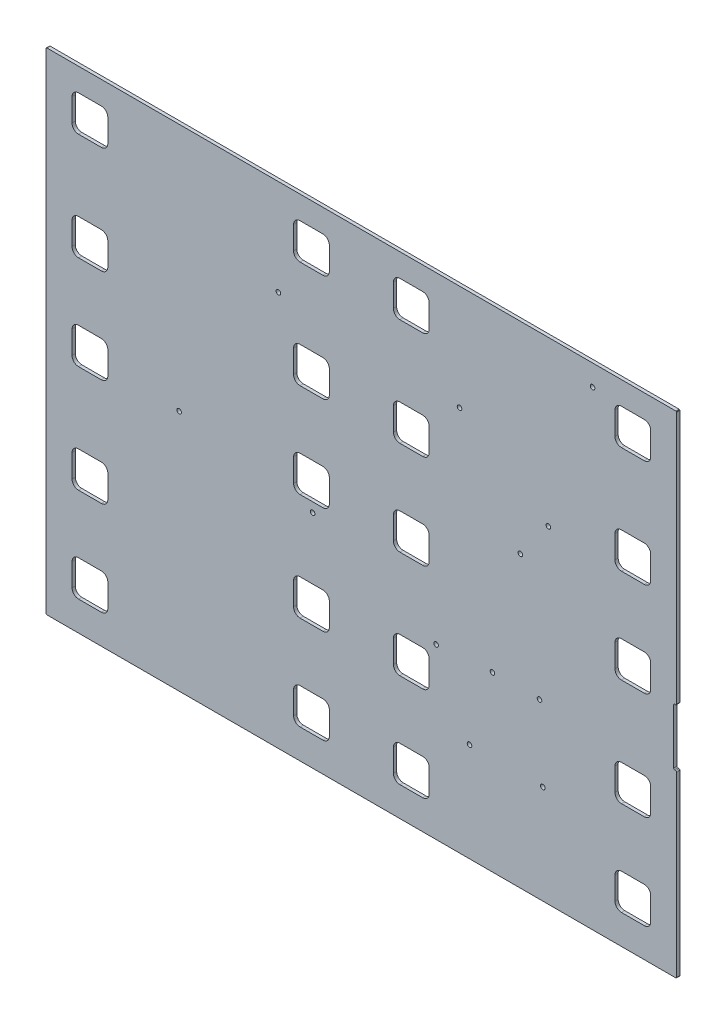
SolidWorks part; units mm, degrees
material "PP Film"
ref_plane "X-Y Datum" through (0, 0, 0) normal (0, 0, 1) x (1, 0, 0)
ref_plane "X-Z Datum" through (0, 0, 0) normal (0, 1, 0) x (1, 0, 0)
ref_plane "Y-Z Datum" through (0, 0, 0) normal (1, 0, 0) x (0, 0, -1)
sketch "Sketch9" plane through (0, 0, 0) normal (0, 0, 1) x (1, 0, 0)
  line L0 (-82.7559, -182.5893) -> (-82.7583, -160.1613) construction
  line L1 (-89.109, -153.8119) -> (-111.537, -153.8143) construction
  line L2 (-117.8863, -160.165) -> (-117.8839, -182.593) construction
  line L3 (-111.5333, -188.9423) -> (-89.1053, -188.9399) construction
  line L4 (475.4266, 171.7866) -> (-142.9187, 171.7216)
  line L12 (-111.5443, -83.8117) -> (-89.1163, -83.8093) construction
  line L13 (-82.767, -77.4587) -> (-82.7693, -55.0307) construction
  line L14 (-89.12, -48.6813) -> (-111.548, -48.6837) construction
  line L15 (-117.8973, -55.0344) -> (-117.895, -77.4624) construction
  line L16 (-82.7877, 120.2549) -> (-82.7901, 142.6829) construction
  line L17 (-89.1408, 149.0323) -> (-111.5688, 149.0299) construction
  line L18 (-117.9181, 142.6792) -> (-117.9157, 120.2512) construction
  line L19 (-111.5651, 113.9019) -> (-89.1371, 113.9043) construction
  line L20 (-111.554, 8.7713) -> (-89.126, 8.7737) construction
  line L21 (-117.9071, 37.5486) -> (-117.9047, 15.1206) construction
  line L22 (-89.1297, 43.9017) -> (-111.5577, 43.8993) construction
  line L23 (-82.7767, 15.1243) -> (-82.7791, 37.5523) construction
  line L24 (-82.7559, -182.5893) -> (-82.7583, -160.1613)
  line L25 (-89.109, -153.8119) -> (-111.537, -153.8143)
  line L26 (-117.8863, -160.165) -> (-117.8839, -182.593)
  line L27 (-111.5333, -188.9423) -> (-89.1053, -188.9399)
  line L28 (-111.5443, -83.8117) -> (-89.1163, -83.8093)
  line L29 (-82.767, -77.4587) -> (-82.7693, -55.0307)
  line L30 (-89.12, -48.6813) -> (-111.548, -48.6837)
  line L31 (-117.8973, -55.0344) -> (-117.895, -77.4624)
  line L32 (-82.7877, 120.2549) -> (-82.7901, 142.6829)
  line L33 (-89.1408, 149.0323) -> (-111.5688, 149.0299)
  line L34 (-117.9181, 142.6792) -> (-117.9157, 120.2512)
  line L35 (-111.5651, 113.9019) -> (-89.1371, 113.9043)
  line L36 (-111.554, 8.7713) -> (-89.126, 8.7737)
  line L37 (-117.9071, 37.5486) -> (-117.9047, 15.1206)
  line L38 (-89.1297, 43.9017) -> (-111.5577, 43.8993)
  line L39 (-82.7767, 15.1243) -> (-82.7791, 37.5523)
  line L40 (-82.7462, -275.1723) -> (-82.7486, -252.7443) construction
  line L41 (-89.0992, -246.3949) -> (-111.5272, -246.3973) construction
  line L42 (-117.8766, -252.748) -> (-117.8742, -275.176) construction
  line L43 (-111.5235, -281.5253) -> (-89.0955, -281.5229) construction
  line L44 (-82.7462, -275.1723) -> (-82.7486, -252.7443)
  line L45 (-89.0992, -246.3949) -> (-111.5272, -246.3973)
  line L46 (-117.8766, -252.748) -> (-117.8742, -275.176)
  line L47 (-111.5235, -281.5253) -> (-89.0955, -281.5229)
  line L174 (475.4266, 171.7866) -> (-142.9187, 171.7216)
  line L243 (-143.3593, 171.281) -> (-143.3088, -310.0568)
  line L244 (-143.3593, 171.281) -> (-143.3088, -310.0568)
  line L245 (-142.8681, -310.4974) -> (475.4773, -310.4324)
  line L246 (-142.8681, -310.4974) -> (475.4773, -310.4324)
  line L247 (475.9178, -309.9918) -> (475.8673, 171.346)
  line L248 (475.9178, -309.9918) -> (475.8673, 171.346)
  arc A0 (-89.1053, -188.9399) -> (-82.7559, -182.5893) centre (-89.1059, -182.5899) ccw construction
  arc A1 (-82.7583, -160.1613) -> (-89.109, -153.8119) centre (-89.1083, -160.1619) ccw construction
  arc A2 (-111.537, -153.8143) -> (-117.8863, -160.165) centre (-111.5363, -160.1643) ccw construction
  arc A3 (-117.8839, -182.593) -> (-111.5333, -188.9423) centre (-111.5339, -182.5923) ccw construction
  arc A4 (-89.1163, -83.8093) -> (-82.767, -77.4587) centre (-89.117, -77.4593) ccw construction
  arc A5 (-82.7693, -55.0307) -> (-89.12, -48.6813) centre (-89.1193, -55.0313) ccw construction
  arc A6 (-111.548, -48.6837) -> (-117.8973, -55.0344) centre (-111.5473, -55.0337) ccw construction
  arc A7 (-117.895, -77.4624) -> (-111.5443, -83.8117) centre (-111.545, -77.4617) ccw construction
  arc A8 (-89.1371, 113.9043) -> (-82.7877, 120.2549) centre (-89.1377, 120.2543) ccw construction
  arc A9 (-82.7901, 142.6829) -> (-89.1408, 149.0323) centre (-89.1401, 142.6823) ccw construction
  arc A10 (-111.5688, 149.0299) -> (-117.9181, 142.6792) centre (-111.5681, 142.6799) ccw construction
  arc A11 (-117.9157, 120.2512) -> (-111.5651, 113.9019) centre (-111.5657, 120.2519) ccw construction
  arc A12 (-82.7791, 37.5523) -> (-89.1297, 43.9017) centre (-89.1291, 37.5517) ccw construction
  arc A13 (-89.126, 8.7737) -> (-82.7767, 15.1243) centre (-89.1267, 15.1237) ccw construction
  arc A14 (-117.9047, 15.1206) -> (-111.554, 8.7713) centre (-111.5547, 15.1213) ccw construction
  arc A15 (-111.5577, 43.8993) -> (-117.9071, 37.5486) centre (-111.5571, 37.5493) ccw construction
  arc A16 (-89.1053, -188.9399) -> (-82.7559, -182.5893) centre (-89.1059, -182.5899) ccw
  arc A17 (-82.7583, -160.1613) -> (-89.109, -153.8119) centre (-89.1083, -160.1619) ccw
  arc A18 (-111.537, -153.8143) -> (-117.8863, -160.165) centre (-111.5363, -160.1643) ccw
  arc A19 (-117.8839, -182.593) -> (-111.5333, -188.9423) centre (-111.5339, -182.5923) ccw
  arc A20 (-89.1163, -83.8093) -> (-82.767, -77.4587) centre (-89.117, -77.4593) ccw
  arc A21 (-82.7693, -55.0307) -> (-89.12, -48.6813) centre (-89.1193, -55.0313) ccw
  arc A22 (-111.548, -48.6837) -> (-117.8973, -55.0344) centre (-111.5473, -55.0337) ccw
  arc A23 (-117.895, -77.4624) -> (-111.5443, -83.8117) centre (-111.545, -77.4617) ccw
  arc A24 (-89.1371, 113.9043) -> (-82.7877, 120.2549) centre (-89.1377, 120.2543) ccw
  arc A25 (-82.7901, 142.6829) -> (-89.1408, 149.0323) centre (-89.1401, 142.6823) ccw
  arc A26 (-111.5688, 149.0299) -> (-117.9181, 142.6792) centre (-111.5681, 142.6799) ccw
  arc A27 (-117.9157, 120.2512) -> (-111.5651, 113.9019) centre (-111.5657, 120.2519) ccw
  arc A28 (-82.7791, 37.5523) -> (-89.1297, 43.9017) centre (-89.1291, 37.5517) ccw
  arc A29 (-89.126, 8.7737) -> (-82.7767, 15.1243) centre (-89.1267, 15.1237) ccw
  arc A30 (-117.9047, 15.1206) -> (-111.554, 8.7713) centre (-111.5547, 15.1213) ccw
  arc A31 (-111.5577, 43.8993) -> (-117.9071, 37.5486) centre (-111.5571, 37.5493) ccw
  arc A32 (-89.0955, -281.5229) -> (-82.7462, -275.1723) centre (-89.0962, -275.1729) ccw construction
  arc A33 (-111.5272, -246.3973) -> (-117.8766, -252.748) centre (-111.5266, -252.7473) ccw construction
  arc A34 (-117.8742, -275.176) -> (-111.5235, -281.5253) centre (-111.5242, -275.1753) ccw construction
  arc A35 (-89.0955, -281.5229) -> (-82.7462, -275.1723) centre (-89.0962, -275.1729) ccw
  arc A36 (-111.5272, -246.3973) -> (-117.8766, -252.748) centre (-111.5266, -252.7473) ccw
  arc A37 (-117.8742, -275.176) -> (-111.5235, -281.5253) centre (-111.5242, -275.1753) ccw
  arc A38 (-82.7486, -252.7443) -> (-89.0992, -246.3949) centre (-89.0986, -252.7449) ccw construction
  arc A39 (-82.7486, -252.7443) -> (-89.0992, -246.3949) centre (-89.0986, -252.7449) ccw
  arc A72 (-142.8681, -310.4974) -> (-143.3088, -310.0568) centre (-144.189, -311.3779) ccw
  arc A108 (-142.8681, -310.4974) -> (-143.3088, -310.0568) centre (-144.189, -311.3779) ccw
  arc A128 (475.9178, -309.9918) -> (475.4773, -310.4324) centre (476.7984, -311.3127) ccw
  arc A132 (475.9178, -309.9918) -> (475.4773, -310.4324) centre (476.7984, -311.3127) ccw
  arc A136 (475.4266, 171.7866) -> (475.8673, 171.346) centre (476.7475, 172.6671) ccw
  arc A140 (475.4266, 171.7866) -> (475.8673, 171.346) centre (476.7475, 172.6671) ccw
  arc A142 (-143.3593, 171.281) -> (-142.9187, 171.7216) centre (-144.2398, 172.6019) ccw
  arc A144 (-143.3593, 171.281) -> (-142.9187, 171.7216) centre (-144.2398, 172.6019) ccw
  dimension "D1" = 0
extrude "Boss-Extrude2" add sketch "Sketch9" along normal blind 3.175 contours L244 L246 L174 A39 L44 A35 L47 A37 L46 A36 L45 A31 L38 A28 L39 A29 L36 A30 L37 A27 L34 A26 L33 A25 L32 A24 L35 A23 L31 A22 L30 A21 L29 A20 L28 A19 L26 A18 L25 A17 L24 A16 L27 | L44 A39 L45 A36 L46 A37 L47 A35 | L26 A19 L27 A16 L24 A17 L25 A18 | L38 A31 L37 A30 L36 A29 L39 A28 | L34 A27 L35 A24 L32 A25 L33 A26 | L31 A23 L28 A20 L29 A21 L30 A22 region at (171.7433, -69.3677, 0) region at (-100.3211, -171.3771, 0) region at (-100.3322, -66.2465, 0) region at (-100.3529, 131.4671, 0) region at (-100.3419, 26.3365, 0) region at (-100.3114, -263.9601, 0)
sketch "Sketch10" plane through (0, 0, 3.175) normal (0, 0, 1) x (1, 0, 0)
  line L9 (476.8831, 172.8027) -> (-144.3755, 172.7375)
  line L10 (-144.3755, 172.7375) -> (-144.3246, -311.5135)
  line L11 (-144.3246, -311.5135) -> (476.934, -311.4483)
  line L12 (-117.8863, -160.165) -> (-117.8839, -182.593)
  line L13 (-111.5333, -188.9423) -> (-89.1053, -188.9399)
  line L14 (-82.7559, -182.5893) -> (-82.7583, -160.1613)
  line L15 (-89.109, -153.8119) -> (-111.537, -153.8143)
  line L16 (-117.8863, -160.165) -> (-117.8839, -182.593)
  line L17 (-111.5333, -188.9423) -> (-89.1053, -188.9399)
  line L18 (-82.7559, -182.5893) -> (-82.7583, -160.1613)
  line L19 (-89.109, -153.8119) -> (-111.537, -153.8143)
  line L20 (-117.8766, -252.748) -> (-117.8742, -275.176)
  line L21 (-89.0992, -246.3949) -> (-111.5272, -246.3973)
  line L22 (-82.7462, -275.1723) -> (-82.7486, -252.7443)
  line L23 (-111.5235, -281.5253) -> (-89.0955, -281.5229)
  line L24 (-117.8766, -252.748) -> (-117.8742, -275.176)
  line L25 (-89.0992, -246.3949) -> (-111.5272, -246.3973)
  line L26 (-82.7462, -275.1723) -> (-82.7486, -252.7443)
  line L27 (-111.5235, -281.5253) -> (-89.0955, -281.5229)
  line L28 (-89.12, -48.6813) -> (-111.548, -48.6837)
  line L29 (-117.8973, -55.0344) -> (-117.895, -77.4624)
  line L30 (-111.5443, -83.8117) -> (-89.1163, -83.8093)
  line L31 (-82.767, -77.4587) -> (-82.7693, -55.0307)
  line L32 (-89.12, -48.6813) -> (-111.548, -48.6837)
  line L33 (-117.8973, -55.0344) -> (-117.895, -77.4624)
  line L34 (-111.5443, -83.8117) -> (-89.1163, -83.8093)
  line L35 (-82.767, -77.4587) -> (-82.7693, -55.0307)
  line L36 (-82.7877, 120.2549) -> (-82.7901, 142.6829)
  line L37 (-111.5651, 113.9019) -> (-89.1371, 113.9043)
  line L38 (-117.9181, 142.6792) -> (-117.9157, 120.2512)
  line L39 (-89.1408, 149.0323) -> (-111.5688, 149.0299)
  line L40 (-82.7877, 120.2549) -> (-82.7901, 142.6829)
  line L41 (-111.5651, 113.9019) -> (-89.1371, 113.9043)
  line L42 (-117.9181, 142.6792) -> (-117.9157, 120.2512)
  line L43 (-89.1408, 149.0323) -> (-111.5688, 149.0299)
  line L44 (-111.554, 8.7713) -> (-89.126, 8.7737)
  line L45 (-82.7767, 15.1243) -> (-82.7791, 37.5523)
  line L46 (-89.1297, 43.9017) -> (-111.5577, 43.8993)
  line L47 (-117.9071, 37.5486) -> (-117.9047, 15.1206)
  line L48 (-111.554, 8.7713) -> (-89.126, 8.7737)
  line L49 (-82.7767, 15.1243) -> (-82.7791, 37.5523)
  line L50 (-89.1297, 43.9017) -> (-111.5577, 43.8993)
  line L51 (-117.9071, 37.5486) -> (-117.9047, 15.1206)
  line L53 (476.934, -311.4483) -> (476.8831, 172.8027)
  arc A4 (-117.8839, -182.593) -> (-111.5333, -188.9423) centre (-111.5339, -182.5923) ccw
  arc A5 (-89.1053, -188.9399) -> (-82.7559, -182.5893) centre (-89.1059, -182.5899) ccw
  arc A6 (-82.7583, -160.1613) -> (-89.109, -153.8119) centre (-89.1083, -160.1619) ccw
  arc A7 (-111.537, -153.8143) -> (-117.8863, -160.165) centre (-111.5363, -160.1643) ccw
  arc A8 (-117.8839, -182.593) -> (-111.5333, -188.9423) centre (-111.5339, -182.5923) ccw
  arc A9 (-89.1053, -188.9399) -> (-82.7559, -182.5893) centre (-89.1059, -182.5899) ccw
  arc A10 (-82.7583, -160.1613) -> (-89.109, -153.8119) centre (-89.1083, -160.1619) ccw
  arc A11 (-111.537, -153.8143) -> (-117.8863, -160.165) centre (-111.5363, -160.1643) ccw
  arc A12 (-111.5272, -246.3973) -> (-117.8766, -252.748) centre (-111.5266, -252.7473) ccw
  arc A13 (-82.7486, -252.7443) -> (-89.0992, -246.3949) centre (-89.0986, -252.7449) ccw
  arc A14 (-89.0955, -281.5229) -> (-82.7462, -275.1723) centre (-89.0962, -275.1729) ccw
  arc A15 (-117.8742, -275.176) -> (-111.5235, -281.5253) centre (-111.5242, -275.1753) ccw
  arc A16 (-111.5272, -246.3973) -> (-117.8766, -252.748) centre (-111.5266, -252.7473) ccw
  arc A17 (-82.7486, -252.7443) -> (-89.0992, -246.3949) centre (-89.0986, -252.7449) ccw
  arc A18 (-89.0955, -281.5229) -> (-82.7462, -275.1723) centre (-89.0962, -275.1729) ccw
  arc A19 (-117.8742, -275.176) -> (-111.5235, -281.5253) centre (-111.5242, -275.1753) ccw
  arc A20 (-111.548, -48.6837) -> (-117.8973, -55.0344) centre (-111.5473, -55.0337) ccw
  arc A21 (-117.895, -77.4624) -> (-111.5443, -83.8117) centre (-111.545, -77.4617) ccw
  arc A22 (-89.1163, -83.8093) -> (-82.767, -77.4587) centre (-89.117, -77.4593) ccw
  arc A23 (-82.7693, -55.0307) -> (-89.12, -48.6813) centre (-89.1193, -55.0313) ccw
  arc A24 (-111.548, -48.6837) -> (-117.8973, -55.0344) centre (-111.5473, -55.0337) ccw
  arc A25 (-117.895, -77.4624) -> (-111.5443, -83.8117) centre (-111.545, -77.4617) ccw
  arc A26 (-89.1163, -83.8093) -> (-82.767, -77.4587) centre (-89.117, -77.4593) ccw
  arc A27 (-82.7693, -55.0307) -> (-89.12, -48.6813) centre (-89.1193, -55.0313) ccw
  arc A28 (-89.1371, 113.9043) -> (-82.7877, 120.2549) centre (-89.1377, 120.2543) ccw
  arc A29 (-117.9157, 120.2512) -> (-111.5651, 113.9019) centre (-111.5657, 120.2519) ccw
  arc A30 (-111.5688, 149.0299) -> (-117.9181, 142.6792) centre (-111.5681, 142.6799) ccw
  arc A31 (-82.7901, 142.6829) -> (-89.1408, 149.0323) centre (-89.1401, 142.6823) ccw
  arc A32 (-89.1371, 113.9043) -> (-82.7877, 120.2549) centre (-89.1377, 120.2543) ccw
  arc A33 (-117.9157, 120.2512) -> (-111.5651, 113.9019) centre (-111.5657, 120.2519) ccw
  arc A34 (-111.5688, 149.0299) -> (-117.9181, 142.6792) centre (-111.5681, 142.6799) ccw
  arc A35 (-82.7901, 142.6829) -> (-89.1408, 149.0323) centre (-89.1401, 142.6823) ccw
  arc A36 (-89.126, 8.7737) -> (-82.7767, 15.1243) centre (-89.1267, 15.1237) ccw
  arc A37 (-82.7791, 37.5523) -> (-89.1297, 43.9017) centre (-89.1291, 37.5517) ccw
  arc A38 (-111.5577, 43.8993) -> (-117.9071, 37.5486) centre (-111.5571, 37.5493) ccw
  arc A39 (-117.9047, 15.1206) -> (-111.554, 8.7713) centre (-111.5547, 15.1213) ccw
  arc A40 (-89.126, 8.7737) -> (-82.7767, 15.1243) centre (-89.1267, 15.1237) ccw
  arc A41 (-82.7791, 37.5523) -> (-89.1297, 43.9017) centre (-89.1291, 37.5517) ccw
  arc A42 (-111.5577, 43.8993) -> (-117.9071, 37.5486) centre (-111.5571, 37.5493) ccw
  arc A43 (-117.9047, 15.1206) -> (-111.554, 8.7713) centre (-111.5547, 15.1213) ccw
  dimension "D2" = 0
  dimension "D3" = 0
  dimension "D4" = 0
  dimension "D5" = 0
  dimension "D6" = 0
extrude "Cut-Extrude6" cut sketch "Sketch10" against normal through all contours L40 A35 L43 A34 L42 A33 L41 A32 | L51 A43 L48 A40 L49 A41 L50 A42 | L35 A27 L32 A24 L33 A25 L34 A26 | L19 A11 L16 A8 L17 A9 L18 A10 | L24 A19 L27 A18 L26 A17 L25 A16 region at (-100.3211, -171.3771, 3.175) region at (-100.3114, -263.9601, 3.175) region at (-100.3322, -66.2465, 3.175) region at (-100.3529, 131.4671, 3.175) region at (-100.3419, 26.3365, 3.175)
pattern_linear "LPattern2" count 2 spacing 217.5764 along (1, 0.0001, 0) of "Cut-Extrude6"
ref_plane "Plane1" through (166.272, 0.0175, 0) normal (-1, -0.0001, 0) x (0, 0, 1)
mirror "Mirror1" about plane through (166.272, 0.0175, 0) normal (-1, -0.0001, 0) of "LPattern2", "Cut-Extrude6"
sketch "Sketch11" plane through (0, 0, 3.175) normal (0, 0, 1) x (1, 0, 0)
  circle A3 centre (295.0226, -140.5889) radius 1.5875
  circle A5 centre (295.0226, -140.5889) radius 1.5875
  circle A7 centre (393.3194, 151.1404) radius 1.5875
  circle A9 centre (393.3194, 151.1404) radius 1.5875
  circle A11 centre (262.6756, 68.3417) radius 1.5875
  circle A13 centre (262.6756, 68.3417) radius 1.5875
  circle A15 centre (84.813, 77.608) radius 1.5875
  circle A17 centre (84.813, 77.608) radius 1.5875
  circle A19 centre (-12.7212, -72.4022) radius 1.5875
  circle A21 centre (-12.7212, -72.4022) radius 1.5875
  circle A23 centre (349.9236, 11.0749) radius 1.5875
  circle A44 centre (349.9236, 11.0749) radius 1.5875
  circle A45 centre (322.4275, -26.052) radius 1.5875
  circle A46 centre (322.4275, -26.052) radius 1.5875
  circle A47 centre (341.2226, -140.584) radius 1.5875
  circle A48 centre (341.2226, -140.584) radius 1.5875
  circle A49 centre (344.4952, -213.3337) radius 1.5875
  circle A50 centre (344.4952, -213.3337) radius 1.5875
  circle A51 centre (118.3901, -93.0713) radius 1.5875
  circle A52 centre (118.3901, -93.0713) radius 1.5875
  circle A53 centre (239.6805, -144.4936) radius 1.5875
  circle A54 centre (239.6805, -144.4936) radius 1.5875
  circle A55 centre (272.4952, -213.3413) radius 1.5875
  circle A56 centre (272.4952, -213.3413) radius 1.5875
  dimension "D1" = 0
  dimension "D2" = 0
  dimension "D3" = 0
  dimension "D4" = 0
  dimension "D5" = 0
  dimension "D6" = 0
  dimension "D7" = 0
  dimension "D8" = 0
  dimension "D9" = 0
  dimension "D10" = 0
  dimension "D11" = 0
  dimension "D12" = 0
sketch "Sketch12" plane through (0, 0, 3.175) normal (0, 0, 1) x (1, 0, 0)
  line L0 (472.9633, -129.0942) -> (472.9585, -83.0942)
  line L1 (472.9632, -127.919) -> (472.9635, -130.2694) construction
  line L2 (472.9584, -81.919) -> (472.9586, -84.2694) construction
  line L3 (475.9178, -309.9918) -> (475.8673, 171.346) construction
  line L4 (472.9609, -78.1542) -> (472.9609, -134.0342)
  line L5 (472.9609, -134.0342) -> (475.8994, -134.0342)
  line L6 (472.9609, -78.1542) -> (475.8935, -78.1542)
  line L9 (475.9178, -309.9918) -> (475.8673, 171.346)
  point P11 (472.9609, -106.0942)
  dimension "D1" = 46
  dimension "D2" = 55.88
extrude "Cut-Extrude8" cut sketch "Sketch12" against normal through all contours L9 region at (474.4287, -106.1035, 3.175)
hole_wizard "M4 Clearance Hole1" positions "Sketch13" profile "Sketch14" hole size "M4" standard "ANSI Metric" end condition through all
sketch "Sketch13" plane through (0, 0, 3.175) normal (0, 0, 1) x (1, 0, 0)
  point P0 (-12.7212, -72.4022)
  point P3 (118.3901, -93.0713)
  point P6 (272.4952, -213.3413)
  point P9 (344.4952, -213.3337)
  point P12 (239.6805, -144.4936)
  point P15 (295.0226, -140.5889)
  point P18 (341.2226, -140.584)
  point P21 (322.4275, -26.052)
  point P24 (349.9236, 11.0749)
  point P27 (262.6756, 68.3417)
  point P30 (393.3194, 151.1404)
  point P33 (84.813, 77.608)
sketch "Sketch14" plane through (-12.7212, -72.4022, 3.175) normal (1, 0, 0) x (0, -1, 0)
  line L0 (0, 0) -> (0, 3.175)
  line L1 (0, 3.175) -> (2.25, 3.175)
  line L2 (2.25, 3.175) -> (2.25, 0)
  line L5 (2.25, 0) -> (0, 0)
  line L11 (0, -6.35) -> (0, 107.95) construction
  dimension "Thru Hole Dia." = 4.5
  dimension "Thru Hole Depth" = 3.175
fillet "Fillet2" radius 0.7937 8 edges at (-142.8681, -310.4974, 1.5875) (-143.3088, -310.0568, 1.5875) (475.4773, -310.4324, 1.5875) (475.9178, -309.9918, 1.5875) (475.8673, 171.346, 1.5875) (475.4266, 171.7866, 1.5875) (-142.9187, 171.7216, 1.5875) (-143.3593, 171.281, 1.5875)
fillet "Fillet3" radius 1.016 4 edges at (475.8935, -78.1542, 1.5875) (472.9609, -78.1542, 1.5875) (475.8994, -134.0342, 1.5875) (472.9609, -134.0342, 1.5875)
